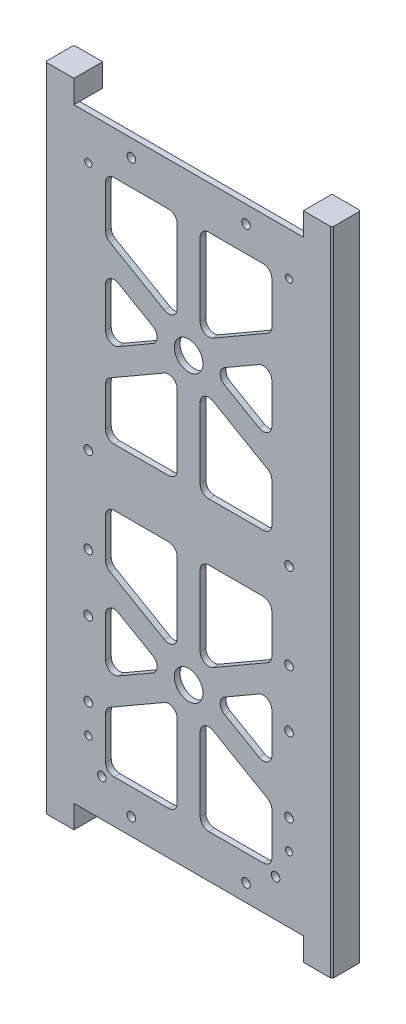
SolidWorks part; units mm, degrees
material "6061-T6 (SS)"
ref_plane "Front Plane" through (0, 0, 0) normal (0, 0, 1) x (1, 0, 0)
ref_plane "Top Plane" through (0, 0, 0) normal (0, 1, 0) x (1, 0, 0)
ref_plane "Right Plane" through (0, 0, 0) normal (1, 0, 0) x (0, 0, -1)
sketch "Sketch1" plane through (0, 0, 0) normal (0, 0, 1) x (1, 0, 0)
  line L1 (0, 0) -> (88, 0)
  line L2 (0, 0) -> (0, 211)
  line L3 (0, 211) -> (88, 211)
  line L4 (88, 0) -> (88, 211)
  dimension "D1" = 88
  dimension "D2" = 211
extrude "Boss-Extrude1" add sketch "Sketch1" along normal blind 2
sketch "Sketch2" plane through (0, 0, 2) normal (0, 0, 1) x (1, 0, 0)
  line L0 (0, 105.5) -> (88, 105.5) construction
  line L1 (0, 211) -> (0, 0) construction
  line L2 (88, 0) -> (88, 211) construction
  line L3 (44, 211) -> (44, 0) construction
  line L4 (88, 211) -> (0, 211) construction
  line L5 (0, 0) -> (88, 0) construction
  line L6 (0, 155.25) -> (88, 155.25) construction
  line L7 (0, 55.75) -> (88, 55.75) construction
  dimension "D1" = 55.75
  dimension "D2" = 55.75
sketch "Sketch3" plane through (0, 0, 2) normal (0, 0, 1) x (1, 0, 0)
  line L0 (0, 155.25) -> (88, 155.25) construction
  line L2 (0, 211) -> (0, 0) construction
  line L3 (15, 196) -> (73, 196)
  line L4 (15, 196) -> (15, 115.5)
  line L5 (15, 115.5) -> (73, 115.5)
  line L6 (73, 196) -> (73, 115.5)
  line L7 (88, 211) -> (0, 211) construction
  line L8 (88, 0) -> (88, 211) construction
  line L9 (0, 105.5) -> (88, 105.5) construction
  line L10 (40, 196) -> (40, 115.5)
  line L11 (48, 196) -> (48, 115.5)
  line L12 (44, 211) -> (44, 0) construction
  line L13 (73, 171.9932) -> (15, 138.5068) construction
  line L14 (15, 171.9932) -> (73, 138.5068) construction
  line L15 (73, 176.612) -> (15, 143.1256)
  line L16 (73, 167.3744) -> (15, 133.888)
  line L17 (15, 176.612) -> (73, 143.1256)
  line L18 (15, 167.3744) -> (73, 133.888)
  circle A0 centre (44, 155.25) radius 5
  dimension "D1" = 10
  dimension "D3" = 15
  dimension "D4" = 15
  dimension "D5" = 15
  dimension "D6" = 10
  dimension "D7" = 8
  dimension "D8" = 4
  dimension "D9" = 30
  dimension "D10" = 30
  dimension "D11" = 8
  dimension "D12" = 4
  dimension "D13" = 4
  dimension "D14" = 8
ref_plane "Plane1" through (0, 105.5, 0) normal (0, -1, 0) x (1, 0, 0)
extrude "Cut-Extrude2" cut sketch "Sketch3" against normal blind 2 contours L18 L11 L5 L6 | L10 L16 L4 L5 | L18 L4 L15 | L16 L17 L6 | L15 L6 L3 L11 | L4 L17 L10 L3 region at (28.6303, 182.3713, 2) region at (59.3697, 182.3713, 2) region at (22, 155.25, 2) region at (28.6744, 128.6415, 2) region at (66, 155.25, 2) region at (59.3256, 128.6415, 2)
sketch "Sketch4" plane through (0, 0, 2) normal (0, 0, 1) x (1, 0, 0)
  line L0 (0, 155.25) -> (88, 155.25) construction
  circle A0 centre (44, 155.25) radius 5
  dimension "D1" = 10
extrude "Cut-Extrude3" cut sketch "Sketch4" against normal through all
mirror "Mirror2" about plane through (0, 105.5, 0) normal (0, -1, 0) of "Cut-Extrude3", "Cut-Extrude2"
fillet "Fillet2" radius 3 44 edges at (73, 67.8744, 1) (73, 43.6256, 1) (52, 55.75, 1) (40, 48.8218, 1) (40, 15, 1) (15, 15, 1) (15, 34.388, 1) (15, 143.1256, 1) (15, 167.3744, 1) (36, 155.25, 1) (15, 115.5, 1) (15, 133.888, 1) (40, 148.3218, 1) (40, 115.5, 1) (48, 196, 1) (73, 196, 1) (48, 162.1782, 1) (73, 115.5, 1) (48, 115.5, 1) (48, 148.3218, 1) (73, 133.888, 1) (15, 196, 1) (40, 196, 1) (40, 162.1782, 1) (15, 176.612, 1) (73, 167.3744, 1) (73, 143.1256, 1) (52, 155.25, 1) (48, 62.6782, 1) (48, 95.5, 1) (73, 95.5, 1) (73, 77.112, 1) (73, 34.388, 1) (73, 15, 1) (48, 15, 1) (48, 48.8218, 1) (40, 62.6782, 1) (15, 77.112, 1) (15, 95.5, 1) (40, 95.5, 1) (15, 43.6256, 1) (15, 67.8744, 1) (36, 55.75, 1) (73, 176.612, 1)
sketch "Sketch5" plane through (0, 0, 2) normal (0, 0, 1) x (1, 0, 0)
  line L0 (88, 0) -> (88, 211) construction
  line L1 (0, 211) -> (0, 0) construction
  line L4 (0, 5.5) -> (88, 5.5) construction
  line L5 (0, 0) -> (88, 0) construction
  line L6 (0, 205.5) -> (88, 205.5) construction
  circle A1 centre (64, 205.5) radius 1.5
  circle A3 centre (64, 5.5) radius 1.5
  circle A4 centre (24, 5.5) radius 1.5
  circle A5 centre (24, 205.5) radius 1.5
  dimension "D5" = 3
  dimension "D2" = 40
  dimension "D3" = 24
  dimension "D1" = 200
  dimension "D4" = 5.5
  dimension "D6" = 3
  dimension "D7" = 40
  dimension "D8" = 24
  dimension "D9" = 3
  dimension "D10" = 24
  dimension "D11" = 24
  dimension "D12" = 3
sketch "Sketch7" plane through (0, 0, 2) normal (0, 0, 1) x (1, 0, 0)
  line L0 (0, 105.5) -> (151.3859, 105.5) construction
  line L5 (0, 211) -> (0, 0) construction
  line L7 (44, 211) -> (44, 0) construction
  line L8 (88, 211) -> (0, 211) construction
  line L9 (0, 0) -> (88, 0) construction
  line L17 (94, 219) -> (84, 219)
  line L53 (88, 0) -> (88, 211)
  line L54 (84, 219) -> (84, 211)
  line L55 (84, 0) -> (88, 0)
  line L56 (94, 0) -> (94, 211)
  line L57 (94, -8) -> (94, 219)
  line L58 (88, 211) -> (0, 211) construction
  line L59 (84, 211) -> (88, 211)
  line L60 (84, -8) -> (84, 0)
  line L61 (94, -8) -> (84, -8)
  line L62 (-6, -8) -> (4, -8)
  line L63 (4, -8) -> (4, 0)
  line L64 (4, 0) -> (0, 0)
  line L65 (0, 0) -> (0, 211)
  line L66 (4, 211) -> (0, 211)
  line L67 (4, 219) -> (4, 211)
  line L68 (-6, 219) -> (4, 219)
  line L69 (-6, -8) -> (-6, 219)
  dimension "D1" = 6
extrude "Boss-Extrude2" add sketch "Sketch7" against normal blind 10
sketch "Sketch53" plane through (0, 0, -8) normal (0, 0, -1) x (-1, 0, 0)
  line L0 (-84, 0) -> (-84, 211)
  line L1 (-84, 211) -> (-90, 211)
  line L2 (-92, 209) -> (-92, 2)
  line L4 (-44, 0) -> (-44, 211)
  line L5 (-4, 0) -> (-84, 0) construction
  line L6 (-84, 211) -> (-4, 211) construction
  line L8 (-90, 0) -> (-84, 0)
  line L9 (4, 209) -> (4, 2)
  line L10 (-4, 211) -> (2, 211)
  line L11 (-4, 0) -> (-4, 211)
  line L12 (2, 0) -> (-4, 0)
  arc A0 (-92, 209) -> (-90, 211) centre (-90, 209) cw
  arc A1 (-90, 0) -> (-92, 2) centre (-90, 2) cw
  arc A2 (4, 209) -> (2, 211) centre (2, 209) ccw
  arc A3 (2, 0) -> (4, 2) centre (2, 2) ccw
  line M9 (-88, 0) -> (-88, 211)
  dimension "D1" = 2
  dimension "D2" = 2
extrude "Cut-Extrude5" cut sketch "Sketch53" against normal blind 8 contours A1 L8 L1 A0 L2 M9 | L12 A3 L9 A2 L10 L11 region at (89.9968, 105.5, -8) region at (0.0036, 105.5, -8)
ref_plane "Plane2" through (44, 0, 0) normal (-1, 0, 0) x (0, 0, 1)
ref_plane "Plane3" through (44, 0, 0) normal (1, 0, 0) x (0, 0, -1)
sketch "Sketch58" plane through (0, 0, 0) normal (0, 0, -1) x (-1, 0, 0)
  line L0 (-4, 0) -> (-84, 0) construction
  line L4 (4, 209) -> (4, 2) construction
  circle A0 centre (-0.7, 13) radius 1.665
  dimension "D1" = 3.33
  dimension "D2" = 4.7
  dimension "D3" = 13
extrude "Cut-Extrude9" cut sketch "Sketch58" against normal blind 1.8 contours A0
mirror "Mirror4" about plane through (44, 0, 0) normal (1, 0, 0) of "Cut-Extrude9"
sketch "Sketch59" plane through (0, -8, 0) normal (0, -1, 0) x (-1, 0, 0)
  line L0 (-94, 8) -> (-94, -2) construction
  line L1 (6, 8) -> (6, -2) construction
  line L2 (-84, 8) -> (-94, 8) construction
  circle A0 centre (-89, 2.4) radius 2
  circle A1 centre (1, 2.4) radius 2
  dimension "D1" = 4
  dimension "D2" = 5
  dimension "D3" = 5
  dimension "D4" = 5.6
extrude "Cut-Extrude10" cut sketch "Sketch59" against normal blind 10
fillet "Fillet3" radius 0.5 4 edges at (-6, 105.5, 2) (-6, 105.5, -8) (94, 105.5, -8) (94, 105.5, 2) profile chamfer
sketch "Sketch60" plane through (0, 0, 2) normal (0, 0, 1) x (1, 0, 0)
  line L0 (44, 211) -> (44, 0) construction
  line L1 (84, 211) -> (4, 211) construction
  line L2 (4, 0) -> (84, 0) construction
  line L3 (-5.5, 219) -> (-5.5, -8) construction
  line L4 (-4, 209) -> (-4, 2) construction
  point P8 (64, 6)
  point P9 (74.3, 13)
  point P10 (79, 23)
  point P11 (79, 33.2)
  point P12 (79, 59.2)
  point P13 (79, 79.2)
  point P14 (9, 196)
  point P15 (9, 79.2)
  point P16 (9, 109.2)
  point P17 (79, 109.2)
  point P18 (9, 59.2)
  point P19 (9, 33.2)
  point P20 (24, 205)
  point P23 (9, 23)
  point P24 (79, 196)
  point P25 (64, 205)
  point P27 (13.7, 13)
  point P28 (24, 6)
  dimension "D1" = 6
  dimension "D2" = 29.5
  dimension "D3" = 15
  dimension "D4" = 14.5
  dimension "D5" = 14.5
  dimension "D6" = 101.8
  dimension "D7" = 131.8
  dimension "D8" = 14.5
  dimension "D9" = 151.8
  dimension "D10" = 14.5
  dimension "D11" = 14.5
  dimension "D12" = 177.8
  dimension "D13" = 188
  dimension "D14" = 14.5
  dimension "D15" = 198
  dimension "D16" = 17.7
  dimension "D17" = 205
  dimension "D18" = 29.5
hole_wizard "Ø3.0mm Dowel Hole1" positions "Sketch61" profile "Sketch62" hole size "Ø3.0" standard "ANSI Metric" end condition through all
sketch "Sketch61" plane through (0, 0, 2) normal (0, 0, 1) x (1, 0, 0)
  point P0 (24, 205)
  point P3 (64, 205)
  point P6 (9, 109.2)
  point P9 (79, 109.2)
  point P12 (9, 79.2)
  point P15 (79, 79.2)
  point P18 (9, 59.2)
  point P21 (79, 59.2)
  point P24 (9, 33.2)
  point P27 (79, 33.2)
  point P30 (13.7, 13)
  point P33 (24, 6)
  point P36 (74.3, 13)
  point P39 (64, 6)
sketch "Sketch62" plane through (24, 205, 2) normal (1, 0, 0) x (0, -1, 0)
  line L0 (0, 0) -> (0, 10)
  line L1 (0, 10) -> (1.5, 10)
  line L2 (1.5, 10) -> (1.5, 0)
  line L5 (1.5, 0) -> (0, 0)
  line L11 (0, -6.35) -> (0, 107.95) construction
  dimension "Thru Hole Dia." = 3
  dimension "Thru Hole Depth" = 10
hole_wizard "Tap Drill for M3x0.5 Tap1" positions "Sketch63" profile "Sketch64" hole size "M3x0.5" standard "ANSI Metric" end condition through all
sketch "Sketch63" plane through (0, 0, 2) normal (0, 0, 1) x (1, 0, 0)
  point P0 (9, 196)
  point P3 (79, 196)
  point P6 (9, 23)
  point P9 (79, 23)
sketch "Sketch64" plane through (9, 196, 2) normal (1, 0, 0) x (0, -1, 0)
  line L0 (0, 0) -> (0, 10)
  line L1 (0, 10) -> (1.25, 10)
  line L2 (1.25, 10) -> (1.25, 0)
  line L5 (1.25, 0) -> (0, 0)
  line L11 (0, -6.35) -> (0, 107.95) construction
  dimension "Thru Hole Dia." = 2.5
  dimension "Thru Hole Depth" = 10
